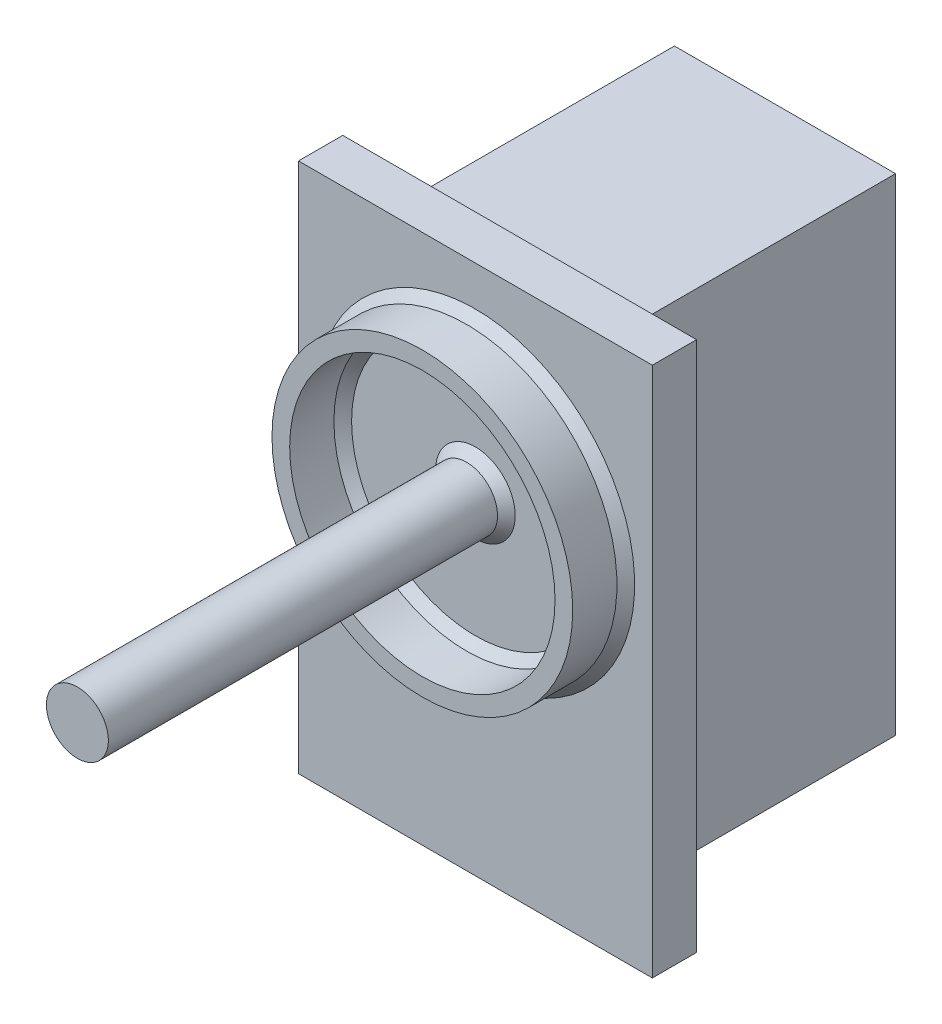
SolidWorks part; units mm, degrees
ref_plane "前基準面" through (0, 0, 0) normal (0, 0, 1) x (1, 0, 0)
ref_plane "上基準面" through (0, 0, 0) normal (0, 1, 0) x (1, 0, 0)
ref_plane "右基準面" through (0, 0, 0) normal (1, 0, 0) x (0, 0, -1)
sketch "草圖1" plane through (0, 0, 0) normal (0, 0, 1) x (1, 0, 0)
  line L1 (-12.5, -27.5) -> (12.5, -27.5)
  line L2 (-12.5, -27.5) -> (-12.5, 27.5)
  line L3 (-12.5, 27.5) -> (12.5, 27.5)
  line L4 (12.5, -27.5) -> (12.5, 27.5)
  line L5 (-12.5, -27.5) -> (12.5, 27.5) construction
  line L6 (-12.5, 27.5) -> (12.5, -27.5) construction
  point P0 (0, 0)
  dimension "D1" = 55
  dimension "D2" = 25
extrude "填料-伸長1" add sketch "草圖1" along normal blind 35
sketch "草圖2" plane through (0, 0, 0) normal (0, 0, -1) x (-1, 0, 0)
  line L1 (-10, 20.25) -> (10, 20.25)
  line L2 (-10, 20.25) -> (-10, -20.25)
  line L3 (-10, -20.25) -> (10, -20.25)
  line L4 (10, 20.25) -> (10, -20.25)
  line L5 (-10, 20.25) -> (10, -20.25) construction
  line L6 (-10, -20.25) -> (10, 20.25) construction
  point P0 (0, 0)
  dimension "D1" = 20
  dimension "D2" = 40.5
extrude "除料-伸長1" cut sketch "草圖2" against normal blind 31.5
sketch "草圖3" plane through (0, 0, 35) normal (0, 0, 1) x (1, 0, 0)
  line L0 (12.5, 27.5) -> (-12.5, 27.5) construction
  circle A0 centre (0, 7.5) radius 3.5
  point P4 (0, 0)
  point P5 (0, 0)
  point P6 (0, 0)
  point P7 (0, 0)
  point P8 (0, 27.5)
  dimension "D1" = 7
  dimension "D2" = 20
extrude "填料-伸長2" add sketch "草圖3" along normal blind 45
sketch "草圖4" plane through (0, 0, 35) normal (0, 0, 1) x (1, 0, 0)
  circle A0 centre (0, 7.5) radius 15
  circle A1 centre (0, 7.5) radius 17
  dimension "D1" = 30
  dimension "D2" = 34
extrude "填料-伸長3" add sketch "草圖4" along normal blind 6
sketch "草圖5" plane through (0, 0, 35) normal (0, 0, 1) x (1, 0, 0)
  line L1 (-20, -30) -> (20, -30)
  line L2 (-20, -30) -> (-20, 30)
  line L3 (-20, 30) -> (20, 30)
  line L4 (20, -30) -> (20, 30)
  line L5 (-20, -30) -> (20, 30) construction
  line L6 (-20, 30) -> (20, -30) construction
  point P0 (0, 0)
  dimension "D1" = 40
  dimension "D2" = 60
extrude "填料-伸長4" add sketch "草圖5" against normal blind 5
chamfer "導角1" distance 1 angle 45 3 edges at (-3.5, 7.5, 35) (-15, 7.5, 35) (-17, 7.5, 35)
chamfer "導角2" distance 1 angle 45 4 edges at (0, 27.5, 30) (12.5, 0, 30) (0, -27.5, 30) (-12.5, 0, 30)
